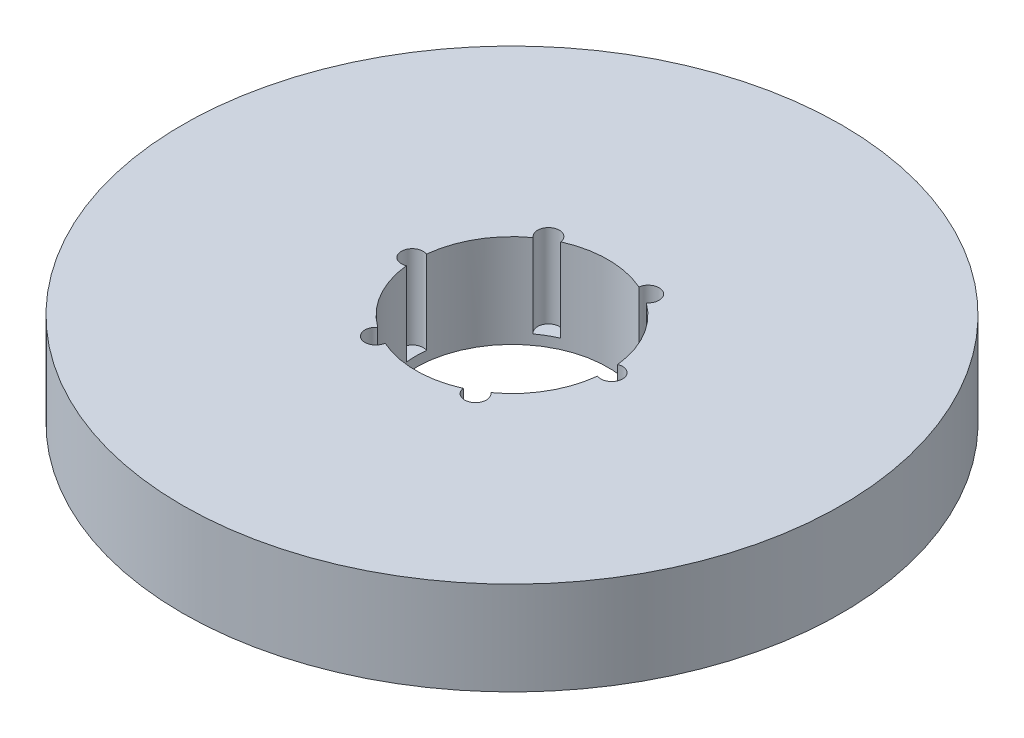
SolidWorks part; units mm, degrees
ref_plane "Front Plane" through (0, 0, 0) normal (0, 0, 1) x (1, 0, 0)
ref_plane "Top Plane" through (0, 0, 0) normal (0, 1, 0) x (1, 0, 0)
ref_plane "Right Plane" through (0, 0, 0) normal (1, 0, 0) x (0, 0, -1)
sketch "Sketch1" plane through (0, 0, 0) normal (0, 1, 0) x (1, 0, 0)
  circle A0 centre (0, 0) radius 60
  dimension "FLANGE_OD" = 120
extrude "Boss-Extrude1" add sketch "Sketch1" along normal blind 17
sketch "Sketch2" plane through (0, 0, 0) normal (0, 1, 0) x (1, 0, 0)
  circle A0 centre (0, 0) radius 17.5
  dimension "BORE_D" = 35
extrude "Cut-Extrude1" cut sketch "Sketch2" along normal through all
sketch "Sketch3" plane through (0, 17, 0) normal (0, 1, 0) x (1, 0, 0)
  circle A0 centre (0, 0) radius 18.1543 construction
  circle A1 centre (-18.1543, 0) radius 1.9812
  dimension "BOLT_D" = 3.9624
  dimension "BOLT_PCD" = 36.3086
extrude "Cut-Extrude2" cut sketch "Sketch3" against normal blind 15.1937
pattern_circular "CirPattern1" count 6 over 360 about axis through (0, 0, 0) along (0, 1, 0) of "Cut-Extrude2"
